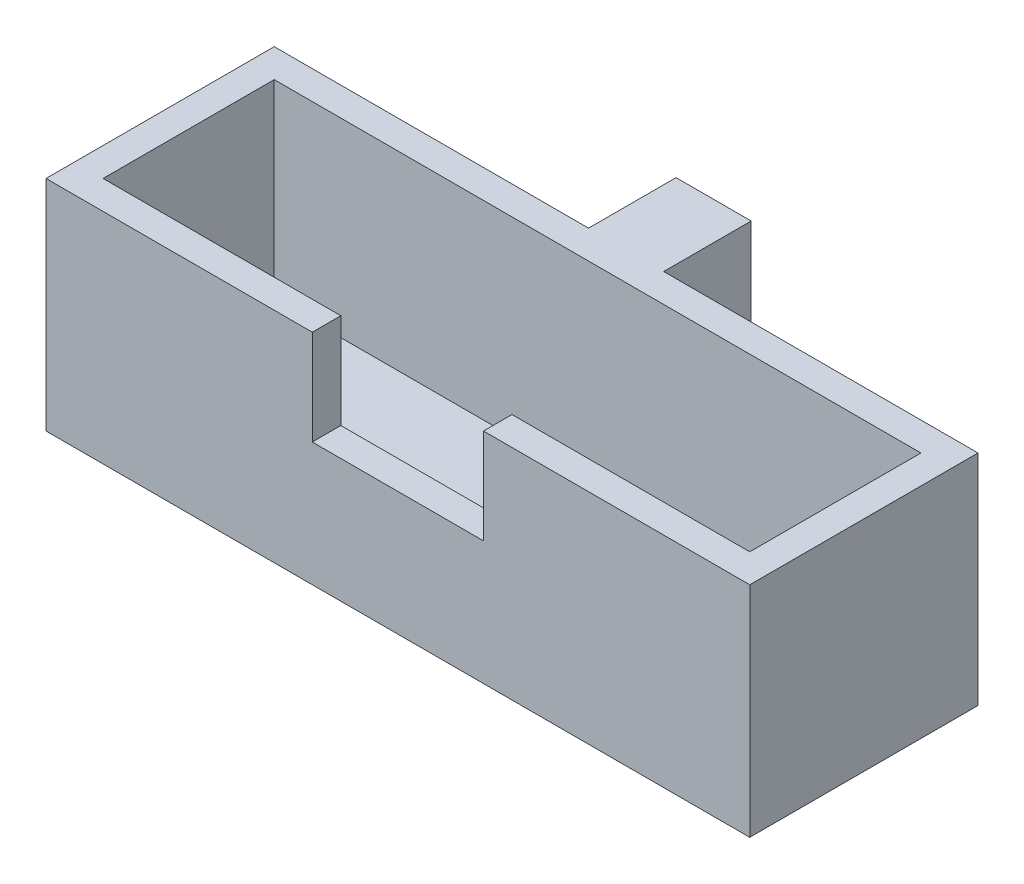
SolidWorks part; units mm, degrees
ref_plane "Front Plane" through (0, 0, 0) normal (0, 0, 1) x (1, 0, 0)
ref_plane "Top Plane" through (0, 0, 0) normal (0, 1, 0) x (1, 0, 0)
ref_plane "Right Plane" through (0, 0, 0) normal (1, 0, 0) x (0, 0, -1)
sketch "Sketch1" plane through (0, 0, 0) normal (0, 1, 0) x (1, 0, 0)
  line L1 (-19.0877, -3.3368) -> (48.9123, -3.3368)
  line L2 (-19.0877, -3.3368) -> (-19.0877, -21.3368)
  line L3 (-19.0877, -21.3368) -> (48.9123, -21.3368)
  line L4 (48.9123, -3.3368) -> (48.9123, -21.3368)
  line L5 (-22.0877, -0.3368) -> (51.9123, -0.3368)
  line L6 (-22.0877, -0.3368) -> (-22.0877, -24.3368)
  line L7 (-22.0877, -24.3368) -> (51.9123, -24.3368)
  line L8 (51.9123, -0.3368) -> (51.9123, -24.3368)
  dimension "D1" = 68
  dimension "D2" = 18
  dimension "D3" = 3
  dimension "D4" = 3
  dimension "D5" = 3
  dimension "D6" = 3
extrude "Boss-Extrude1" add sketch "Sketch1" along normal blind 20
extrude "Boss-Extrude2" add sketch "Sketch1<3>" against normal blind 3 contours L4 L1 L2 L3 | L8 L5 L6 L7 L1 L4 L3 L2 region at (14.9123, 0, 12.3368) region at (14.9123, 0, 1.1148)
sketch "Sketch1<3>" plane through (0, 0, 0) normal (0, 1, 0) x (1, 0, 0) same geometry as "Sketch1"
sketch "Sketch4" plane through (0, 0, 21.3368) normal (0, 0, -1) x (-1, 0, 0)
  line L0 (19.0877, 20) -> (19.0877, 0) construction
  line L1 (-5.9123, 20) -> (-23.9123, 20)
  line L2 (-5.9123, 20) -> (-5.9123, 10)
  line L3 (-5.9123, 10) -> (-23.9123, 10)
  line L4 (-23.9123, 20) -> (-23.9123, 10)
  line L5 (-48.9123, 20) -> (-48.9123, 0) construction
  line L6 (19.0877, 20) -> (-48.9123, 20) construction
  line L7 (19.0877, 0) -> (-48.9123, 0) construction
  dimension "D1" = 25
  dimension "D2" = 25
  dimension "D3" = 0
  dimension "D4" = 10
extrude "Cut-Extrude1" cut sketch "Sketch4" against normal up to next
sketch "Sketch5" plane through (0, 0, 0.3368) normal (0, 0, -1) x (-1, 0, 0)
  line L1 (-51.9123, 20) -> (22.0877, 20)
  line L2 (-51.9123, 20) -> (-51.9123, -3)
  line L3 (-51.9123, -3) -> (22.0877, -3)
  line L4 (22.0877, 20) -> (22.0877, -3)
  line L9 (-18.8623, 20) -> (-10.9623, 20)
  line L10 (-18.8623, 20) -> (-18.8623, -3)
  line L11 (-18.8623, -3) -> (-10.9623, -3)
  line L12 (-10.9623, 20) -> (-10.9623, -3)
  dimension "D2" = 74
  dimension "D1" = 33.05
  dimension "D3" = 33.05
extrude "Boss-Extrude3" add sketch "Sketch5" along normal blind 9.2 contours L12 L1 L10 L3 region at (14.9123, 8.5, 0.3368)
equation "\"camera thickness\"= 18"
equation "\"camera height\"= 40"
equation "\"camera width\"= 68"
equation "\"side to camera\"= 25"
equation "\"D1@Sketch1\"=\"camera width\""
equation "\"D2@Sketch1\"=\"camera thickness\""
equation "\"mount thickness\"=3"
equation "\"D3@Sketch1\"=\"mount thickness\""
equation "\"D4@Sketch1\"=\"mount thickness\""
equation "\"D5@Sketch1\"=\"mount thickness\""
equation "\"D6@Sketch1\"=\"mount thickness\""
equation "\"D1@Boss-Extrude1\"=\"camera height\"/2"
equation "\"D1@Boss-Extrude2\"=\"mount thickness\""
equation "\"D1@Sketch4\"=\"side to camera\""
equation "\"D2@Sketch4\"=\"side to camera\""
equation "\"D4@Sketch4\"=\"camera height\"/4"
equation "\"light thickness\"= 14.1"
equation "\"light inner diameter\"= 66"
equation "\"rail width\"= 79"
equation "\"D3@Sketch5\"=\"D1@Sketch5\""
